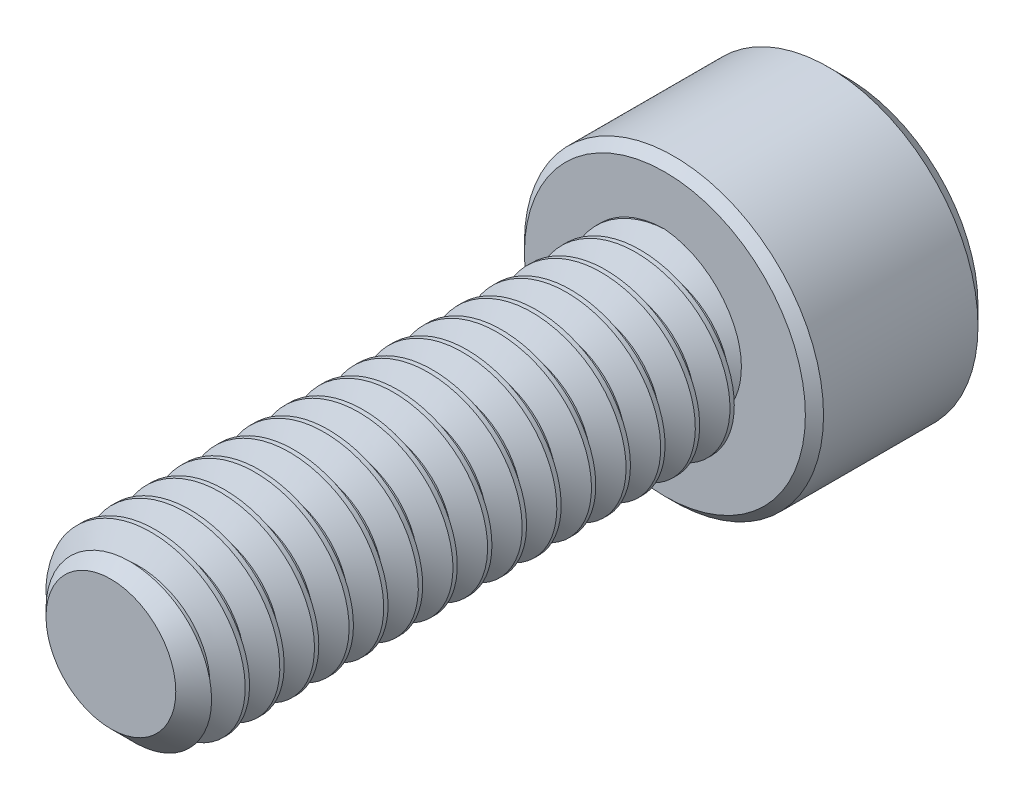
SolidWorks part; units mm, degrees
note: '?' marks a value the reader was unsure of.
ref_plane "Front Plane" through (0, 0, 0) normal (0, 0, 1) x (1, 0, 0)
ref_plane "Top Plane" through (0, 0, 0) normal (0, 1, 0) x (1, 0, 0)
ref_plane "Right Plane" through (0, 0, 0) normal (1, 0, 0) x (0, 0, -1)
sketch "Sketch1" plane through (0, 0, 0) normal (0, 0, 1) x (1, 0, 0)
  line L0 (0, 2.0828) -> (0, -2.0828) construction
  circle A0 centre (0, 0) radius 2.0828
  dimension "OD" = 4.1656
extrude "Extrude1" add sketch "Sketch1" against normal blind 12.7
sketch "Sketch2" plane through (0, 0, 0) normal (0, 0, 1) x (1, 0, 0)
  circle A0 centre (0, 0) radius 2.0828 construction
  circle A1 centre (0, 0) radius 2.0828
curve "Helix/Spiral1" pitch 0.7937 height 13.4937 turns 17 parameters "pitch"=0.7937
chamfer "Chamfer3" distance 0.5953 angle 45 1 edges at (2.0828, 0, 0)
sketch "Sketch3" plane through (0, 0, 0) normal (1, 0, 0) x (0, 0, -1)
  line L0 (-0.6945, 2.0828) -> (-0.3969, 1.5672)
  line L1 (-0.3969, 1.5672) -> (-0.2977, 1.5672)
  line L2 (-0.2977, 1.5672) -> (0, 2.0828)
  line L3 (-0.6945, 2.0828) -> (0, 2.0828)
  line L4 (-0.3473, 2.0828) -> (-0.3473, 1.5672) construction
  line L5 (-0.5457, 1.825) -> (-0.1488, 1.825) construction
  line L6 (0, 2.0828) -> (0, -2.0828) construction
  dimension "D1" = 0.0992
  dimension "D2" = 0.3969
  dimension "D3" = 60
sweep "Cut-Sweep1" cut profiles "Sketch3" path "Helix/Spiral1"
sketch "Sketch6" plane through (0, 0, -12.7) normal (0, 0, -1) x (-1, 0, 0)
  circle A0 centre (0, 0) radius 3.429
  dimension "head dia" = 6.858
extrude "Extrude2" add sketch "Sketch6" along normal blind 4.1656
sketch "Sketch7" plane through (0, 0, -16.8656) normal (0, 0, -1) x (-1, 0, 0)
  line L1 (0, 2.0622) -> (-1.7859, 1.0311)
  line L2 (-1.7859, 1.0311) -> (-1.7859, -1.0311)
  line L3 (-1.7859, -1.0311) -> (0, -2.0622)
  line L4 (0, -2.0622) -> (1.7859, -1.0311)
  line L5 (1.7859, -1.0311) -> (1.7859, 1.0311)
  line L6 (1.7859, 1.0311) -> (0, 2.0622)
  circle A0 centre (0, 0) radius 1.7859 construction
  dimension "hex dia" = 3.5719
extrude "Cut-Extrude1" cut sketch "Sketch7" against normal blind 2.6789
sketch "Sketch8" plane through (0, 0, -16.8656) normal (0, 0, -1) x (-1, 0, 0)
  circle A0 centre (0, 0) radius 2.0622
extrude "Cut-Extrude2" cut sketch "Sketch8" against normal blind 0.4166 draft 45
chamfer "Chamfer1" distance 0.4166 angle 45 1 edges at (-3.429, 0, -16.8656)
chamfer "Chamfer2" distance 0.2083 angle 45 1 edges at (-3.429, 0, -12.7)
sketch "Sketch9" plane through (0, 0, 0) normal (1, 0, 0) x (0, 0, -1)
  line L0 (0, 2.0828) -> (0, -2.0828) construction
  line L1 (4.3656, 2.0828) -> (4.3656, -2.0828) construction
  line L2 (12.7, 3.429) -> (12.7, -3.429) construction
  line L3 (16.8656, 3.429) -> (16.8656, -3.429) construction
  line L4 (16.8656, 0) -> (0, 0) construction
  dimension "D1" = 4.3656
  dimension "D2" = 4.1656
  dimension "D3" = 6.858
  dimension "D4" = 12.7
ref_axis "Axis1" through (0, 0, -16.449) along (0, 0, 1)?
equation "\"D3@Helix/Spiral1\" = \"screw length@Extrude1\"+\"pitch@Helix/Spiral1\""
equation "\"D1@Sketch3\" = \"pitch@Helix/Spiral1\"*.125"
equation "\"D2@Sketch3\" = \"pitch@Helix/Spiral1\"*.5"
equation "\"D1@Cut-Extrude1\" = \"hex dia@Sketch7\"*.75"
equation "\"D1@Chamfer1\" = \"head depth@Extrude2\"/10"
equation "\"D1@Sketch9\" = \"pitch@Helix/Spiral1\"*5.5"
equation "\"D1@Chamfer2\" = \"D1@Chamfer1\"/2"
equation "\"D1@Cut-Extrude2\" = \"D1@Chamfer2\"*2"
equation "\"D1@Chamfer3\" = \"pitch@Helix/Spiral1\"*.750"
equation "\"D2@Sketch9\" = \"head depth@Extrude2\""
equation "\"D3@Sketch9\" = \"head dia@Sketch6\""
equation "\"D4@Sketch9\" = \"screw length@Extrude1\""
